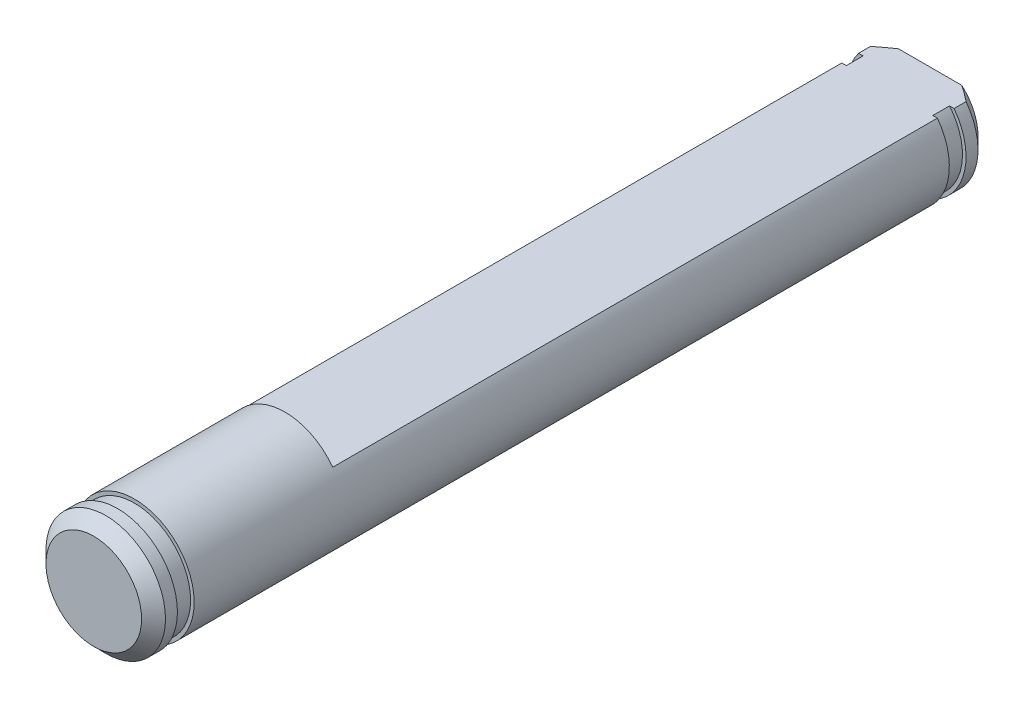
SolidWorks part; units mm, degrees
material "Chromowa stal nierdzewna"
ref_plane "Płaszczyzna przednia" through (0, 0, 0) normal (0, 0, 1) x (1, 0, 0)
ref_plane "Płaszczyzna górna" through (0, 0, 0) normal (0, 1, 0) x (1, 0, 0)
ref_plane "Płaszczyzna prawa" through (0, 0, 0) normal (1, 0, 0) x (0, 0, -1)
sketch "Szkic1" plane through (0, 0, 0) normal (0, 0, 1) x (1, 0, 0)
  circle A0 centre (0, 0) radius 2.5
  dimension "D1" = 5
extrude "Dodanie-wyciągnięcie1" add sketch "Szkic1" along normal blind 35
chamfer "Sfazowanie1" distance 0.5 angle 45 2 edges at (2.5, 0, 0) (2.5, 0, 35)
sketch "Szkic2" plane through (0, 0, 35) normal (0, 0, 1) x (1, 0, 0)
  circle A0 centre (0, 0) radius 2.5
  circle A1 centre (0, 0) radius 2.35
  dimension "D1" = 5
  dimension "D2" = 4.7
extrude "Wytnij-wyciągnięcie1" cut sketch "Szkic2" against normal blind 0.7 from offset 1 offset against normal yes
sketch "Szkic3" plane through (0, 0, 0) normal (0, 0, -1) x (-1, 0, 0)
  circle A0 centre (0, 0) radius 2.5
  circle A1 centre (0, 0) radius 2.35
  dimension "D1" = 4.7
  dimension "D2" = 5
extrude "Wytnij-wyciągnięcie2" cut sketch "Szkic3" against normal blind 0.7 from offset 1 offset against normal yes
sketch "Szkic4" plane through (0, 0, 35) normal (0, 0, 1) x (1, 0, 0)
  line L0 (-2, 1.5) -> (2, 1.5)
  arc A0 (2, 1.5) -> (-2, 1.5) centre (0, 0) ccw
  dimension "D1" = 5
  dimension "D2" = 1.5
extrude "Wytnij-wyciągnięcie3" cut sketch "Szkic4" along normal blind 27 from offset 35 offset against normal yes
